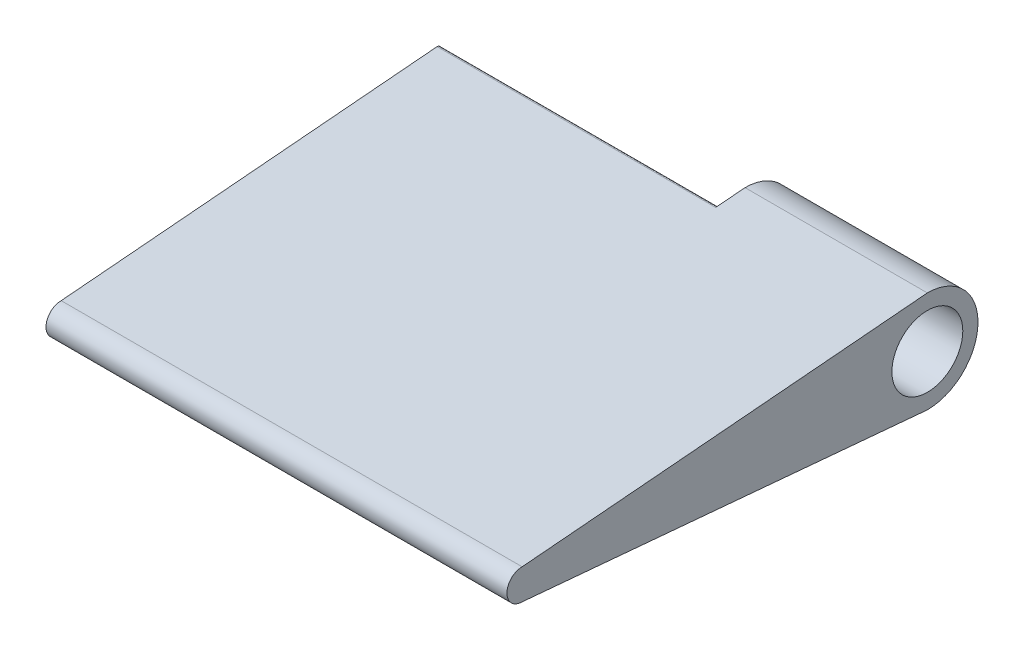
SolidWorks part; units mm, degrees
ref_plane "Front Plane" through (0, 0, 0) normal (0, 0, 1) x (1, 0, 0)
ref_plane "Top Plane" through (0, 0, 0) normal (0, 1, 0) x (1, 0, 0)
ref_plane "Right Plane" through (0, 0, 0) normal (1, 0, 0) x (0, 0, -1)
sketch "Sketch1" plane through (0, 0, 0) normal (1, 0, 0) x (0, 0, -1)
  line L0 (-40, 1.5892) -> (0, 5)
  line L1 (-40, -1.4108) -> (0, -5)
  circle A0 centre (0, 0) radius 5
  circle A1 centre (0, 0) radius 3.5
  circle A2 centre (-40, 0.0892) radius 1.5
  dimension "D1" = 10
  dimension "D2" = 7
  dimension "D3" = 3
  dimension "D4" = 40
extrude "Boss-Extrude1" add sketch "Sketch1" against normal blind 27.5 contours A2 L1 A0 L0 | A2 region at (0, 0.0423, 18.6183)
extrude "Boss-Extrude2" add sketch "Sketch1<3>" along normal blind 18 contours A2 | A2 L1 A0 L0 | L0 A0 L1 A1 region at (0, 0.0423, 18.6183) region at (0, 0.0892, 40) region at (0, 4.823, 0.4113)
sketch "Sketch1<3>" plane through (0, 0, 0) normal (1, 0, 0) x (0, 0, -1) same geometry as "Sketch1"
fillet "Fillet1" radius 0.3 2 edges at (-13.75, -4.9201, 0.8901) (-13.75, 4.9278, 0.8466)
sketch "Sketch2" plane through (0, 0, 0) normal (0, 0, 1) x (1, 0, 0)
  line L0 (-27.5, -1.5378) -> (-9.5, -1.5378)
  line L1 (-27.5, -1.4108) -> (-27.5, -4.7378) construction
  line L2 (-9.5, -1.5378) -> (-9.5, -6.987)
  line L3 (-9.5, -6.987) -> (-27.5, -6.987)
  line L4 (-27.5, -6.987) -> (-27.5, -1.5378)
  line L5 (-27.5, -4.7378) -> (0, -4.7378) construction
  dimension "D1" = 18
  dimension "D2" = 3.2
extrude "Cut-Extrude2" cut sketch "Sketch2" along normal blind 48
sketch "Sketch3" plane through (0, -4.9601, 0.4451) normal (0, -0.996, 0.0894) x (1, 0, 0)
  line L8 (-27.5, 38.2936) -> (-9.5, 38.2936)
  line L9 (-9.5, 38.2936) -> (-9.5, 2.4875)
  line L10 (-9.5, 2.4875) -> (0, 2.4875)
  line L11 (0, 2.4875) -> (0, -0.4469)
  line L12 (0, -0.4469) -> (18, -0.4469)
  line L13 (18, -0.4469) -> (18, 39.7139)
  line L14 (18, 39.7139) -> (-27.5, 39.7139)
  line L15 (-27.5, 39.7139) -> (-27.5, 38.2936)
  line L16 (-27.5, 38.2936) -> (-9.5, 38.2936)
  line L17 (-9.5, 38.2936) -> (-9.5, 2.4875)
  line L18 (-9.5, 2.4875) -> (0, 2.4875)
  line L19 (0, 2.4875) -> (0, -0.4469)
  line L20 (0, -0.4469) -> (18, -0.4469)
  line L21 (18, -0.4469) -> (18, 39.7139)
  line L22 (18, 39.7139) -> (-27.5, 39.7139)
  line L23 (-27.5, 39.7139) -> (-27.5, 38.2936)
  dimension "D2" = 18
  dimension "D3" = 45.5
  dimension "D1" = 0
ref_plane "Plane1" through (0, 0, -10) normal (0, 0, 1) x (1, 0, 0)
